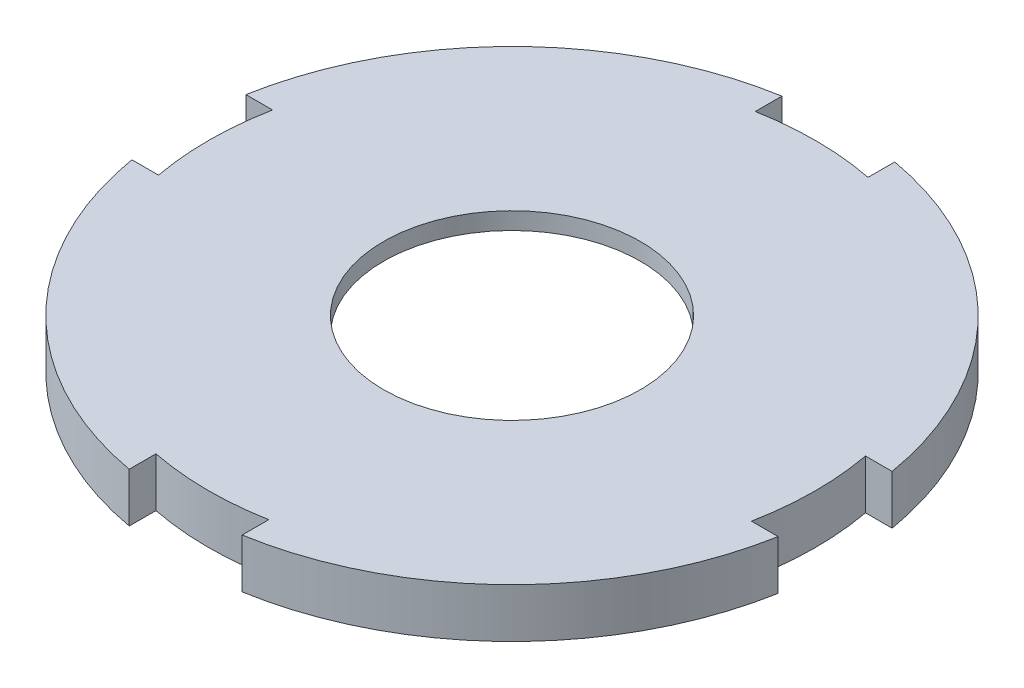
SolidWorks part; units mm, degrees
ref_plane "Front Plane" through (0, 0, 0) normal (0, 0, 1) x (1, 0, 0)
ref_plane "Top Plane" through (0, 0, 0) normal (0, 1, 0) x (1, 0, 0)
ref_plane "Right Plane" through (0, 0, 0) normal (1, 0, 0) x (0, 0, -1)
sketch "Sketch1" plane through (0, 0, 0) normal (0, 1, 0) x (1, 0, 0)
  line L0 (35.4054, 6.5405) -> (38.5653, 6.5405)
  line L1 (35.3329, -6.9215) -> (38.4988, -6.9215)
  line L2 (-3.4925, 0) -> (3.4925, 0) construction
  line L3 (6.5405, -35.4054) -> (6.5405, -38.5653)
  line L4 (-6.9215, -35.3329) -> (-6.9215, -38.4988)
  line L5 (-35.4054, -6.5405) -> (-38.5653, -6.5405)
  line L6 (-35.3329, 6.9215) -> (-38.4988, 6.9215)
  line L7 (-6.5405, 35.4054) -> (-6.5405, 38.5653)
  line L8 (6.9215, 35.3329) -> (6.9215, 38.4988)
  arc A1 (-38.5653, -6.5405) -> (-6.9215, -38.4988) centre (0, 0) ccw
  circle A2 centre (0, 0) radius 15.24
  arc A3 (-35.3329, 6.9215) -> (-35.4054, -6.5405) centre (0, 0) ccw
  arc A4 (6.9215, 35.3329) -> (-6.5405, 35.4054) centre (0, 0) ccw
  arc A5 (35.3329, -6.9215) -> (35.4054, 6.5405) centre (0, 0) ccw
  arc A6 (-6.9215, -35.3329) -> (6.5405, -35.4054) centre (0, 0) ccw
  arc A7 (6.5405, -38.5653) -> (38.4988, -6.9215) centre (0, 0) ccw
  arc A8 (38.5653, 6.5405) -> (6.9215, 38.4988) centre (0, 0) ccw
  arc A9 (-6.5405, 38.5653) -> (-38.4988, 6.9215) centre (0, 0) ccw
  point P26 (0, 0)
  dimension "D1" = 78.232
  dimension "D2" = 72.009
  dimension "D6" = 30.48
  dimension "D3" = 13.462
  dimension "D4" = 6.5405
  dimension "D5" = 4
ref_axis "Axis1" through (41.0751, 0, 0) along (-1, 0, 0)
ref_plane "Plane2" through (0, 0, 0) normal (0, -0.9903, 0.1392) x (-1, 0, 0)
ref_plane "Plane3" through (0, 6.2882, -0.8837) normal (0, -0.9903, 0.1392) x (-1, 0, 0)
extrude "Boss-Extrude2" add sketch "Sketch1" along normal blind 5.842
sketch "Sketch2" plane through (0, 0, 0) normal (0, -1, 0) x (1, 0, 0)
  line L3 (17.3777, -10.033) -> (-0.2866, -40.6283)
  line L4 (-4.5397, -40.3749) -> (8.1962, -18.3157)
  line L5 (3.2131, 0) -> (-3.2131, 0) construction
  arc A3 (8.1962, -18.3157) -> (17.3777, -10.033) centre (0, 0) cw
  arc A4 (-0.2866, -40.6283) -> (-4.5397, -40.3749) centre (0, 0) cw
  point P4 (8.5456, -25.3307)
  dimension "D1" = 20.066
  dimension "D2" = 3.81
  dimension "D3" = 60
extrude "Cut-Extrude1" cut sketch "Sketch2" against normal blind 3.81
sketch "Sketch3" plane through (0, 0, 0) normal (0, -1, 0) x (1, 0, 0)
  circle A0 centre (0, 0) radius 31.75
extrude "Cut-Extrude2" cut sketch "Sketch3" against normal blind 1.27
